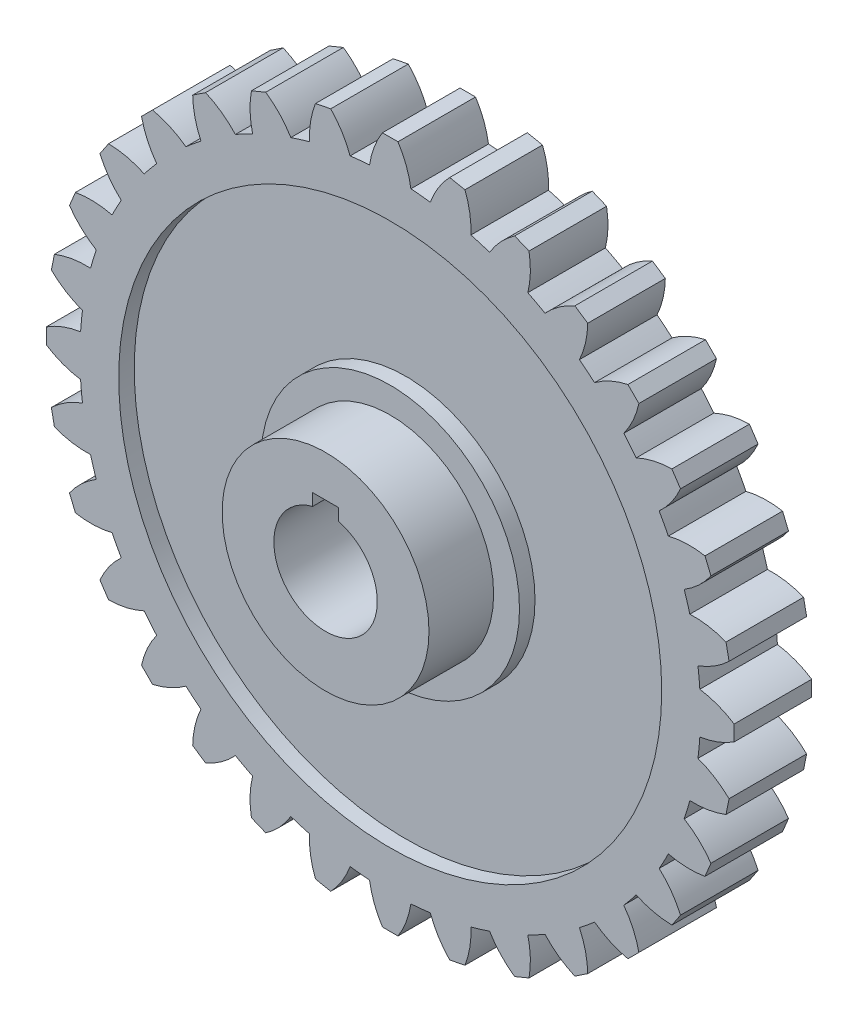
SolidWorks part; units mm, degrees
ref_plane "Front Plane" through (0, 0, 0) normal (0, 0, 1) x (1, 0, 0)
ref_plane "Top Plane" through (0, 0, 0) normal (0, 1, 0) x (1, 0, 0)
ref_plane "Right Plane" through (0, 0, 0) normal (1, 0, 0) x (0, 0, -1)
sketch "Sketch1" plane through (0, 0, 0) normal (0, 0, 1) x (1, 0, 0)
  circle A0 centre (0, 0) radius 60
  dimension "D1" = 120
extrude "Boss-Extrude1" add sketch "Sketch1" along normal mid plane 15
sketch "Sketch2" plane through (0, 0, 7.5) normal (0, 0, 1) x (1, 0, 0)
  line L0 (0, 60) -> (0, 66.5) construction
  line L1 (-1.5, 66.5) -> (1.5, 66.5)
  circle A0 centre (0, 0) radius 60 construction
  arc A1 (4, 59.8665) -> (-4, 59.8665) centre (0, 0) ccw
  arc A2 (-1.5, 66.5) -> (-4, 59.8665) centre (12.8082, 57.3198) ccw
  arc A3 (1.5, 66.5) -> (4, 59.8665) centre (-12.8082, 57.3198) cw
  point P7 (0, 66.5)
  dimension "D3" = 17
  dimension "D1" = 6.5
  dimension "D2" = 3
  dimension "D4" = 8
extrude "Boss-Extrude2" add sketch "Sketch2" against normal up to surface (15 mm away) up to face at (60, 0, -7.5)
pattern_circular "CirPattern1" count 32 over 360 about axis through (0, 0, -7.5) along (0, 0, 1) of "Boss-Extrude2"
sketch "Sketch3" plane through (0, 0, 0) normal (0, 0, 1) x (1, 0, 0)
  circle A0 centre (0, 0) radius 20
  dimension "D1" = 40
extrude "Boss-Extrude3" add sketch "Sketch3" along normal mid plane 40
sketch "Sketch4" plane through (0, 0, 20) normal (0, 0, 1) x (1, 0, 0)
  line L0 (0, 0) -> (0, 12) construction
  line L1 (-2.5, 12) -> (2.5, 12)
  line L2 (2.5, 12) -> (2.5, 9.6825)
  line L3 (-2.5, 12) -> (-2.5, 9.6825)
  arc A0 (-2.5, 9.6825) -> (2.5, 9.6825) centre (0, 0) ccw
  point P7 (0, 12)
  dimension "D2" = 20
  dimension "D1" = 5
  dimension "D3" = 12
extrude "Cut-Extrude1" cut sketch "Sketch4" against normal through all both and the other way through all
sketch "Sketch5" plane through (0, 0, 0) normal (0, 0, 1) x (1, 0, 0)
  circle A1 centre (0, 0) radius 52.5
  circle A2 centre (0, 0) radius 25
  circle A3 centre (0, 0) radius 25
  dimension "D2" = 105
  dimension "D1" = 5
extrude "Cut-Extrude2" cut sketch "Sketch5" against normal blind 3 and the other way through all from surface starting at face at (20, 0, 7.5)
mirror "Mirror1" about plane through (0, 0, 0) normal (0, 0, 1) of "Cut-Extrude2"
